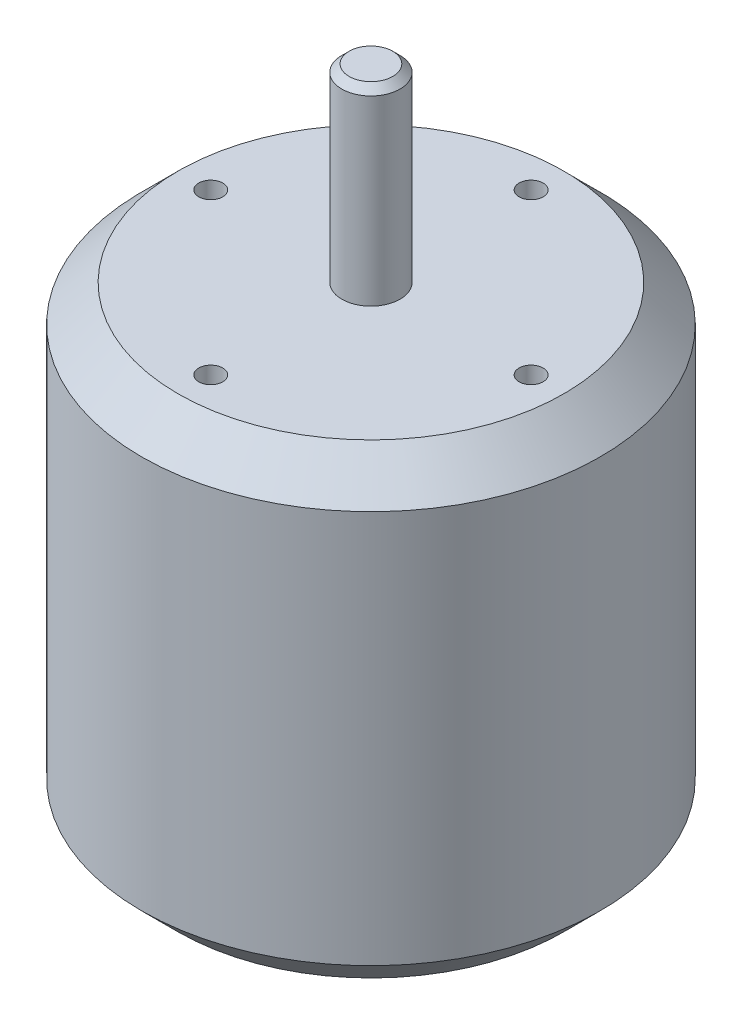
SolidWorks part; units mm, degrees
material "7050-T7451"
ref_plane "Front Plane" through (0, 0, 0) normal (0, 0, 1) x (1, 0, 0)
ref_plane "Top Plane" through (0, 0, 0) normal (0, 1, 0) x (1, 0, 0)
ref_plane "Right Plane" through (0, 0, 0) normal (1, 0, 0) x (0, 0, -1)
sketch "Sketch1" plane through (0, 0, 0) normal (0, 1, 0) x (1, 0, 0)
  circle A0 centre (0, 0) radius 31.5
  dimension "D1" = 63
extrude "Boss-Extrude1" add sketch "Sketch1" along normal blind 64
sketch "Sketch2" plane through (0, 64, 0) normal (0, 1, 0) x (1, 0, 0)
  circle A0 centre (0, 0) radius 4
  dimension "D1" = 8
extrude "Boss-Extrude2" add sketch "Sketch2" along normal blind 26
chamfer "Chamfer3" distance 1 angle 45 1 edges at (0, 90, 4)
sketch "Sketch3" plane through (0, 0, 0) normal (1, 0, 0) x (0, 0, -1)
  line L0 (3, 90) -> (-3, 90) construction
  line L1 (-1.5, 67.5) -> (1.5, 67.5)
  line L2 (-1.5, 67.5) -> (-1.5, 86.5)
  line L3 (-1.5, 86.5) -> (1.5, 86.5)
  line L4 (1.5, 67.5) -> (1.5, 86.5)
  line L5 (-1.5, 67.5) -> (1.5, 86.5) construction
  line L6 (-1.5, 86.5) -> (1.5, 67.5) construction
  line L8 (0, 90) -> (0, 64) construction
  line L9 (31.5, 64) -> (-31.5, 64) construction
  point P0 (0, 77)
  dimension "D1" = 13
  dimension "D2" = 19
  dimension "D3" = 3
extrude "Cut-Extrude1" cut sketch "Sketch3" against normal up to next
fillet "Fillet1" radius 1.5 4 edges at (-1.854, 67.5, -1.5) (-1.854, 67.5, 1.5) (-1.854, 86.5, -1.5) (-1.854, 86.5, 1.5)
sketch "Sketch7" plane through (0, 64, 0) normal (0, 1, 0) x (1, 0, 0)
  line L0 (0, 22) -> (0, 0) construction
  circle A0 centre (0, 0) radius 22 construction
  dimension "D1" = 44
hole_wizard "M4 Tapped Hole1" positions "3DSketch3" profile "Sketch10" tap size "M4" standard "DIN"
sketch3d "3DSketch3"
  point P0 (0, 64, -22)
sketch "Sketch10" plane through (0, 64, -22) normal (1, 0, 0) x (0, 0, 1)
  line L0 (0, 0) -> (0, 13.0914)
  line L1 (0, 13.0914) -> (1.65, 12.1)
  line L2 (1.65, 12.1) -> (1.65, 0)
  line L5 (1.65, 0) -> (0, 0)
  line L10 (0, 13.0914) -> (-1.65, 12.1) construction
  line L11 (0, -6.35) -> (0, 107.95) construction
  dimension "Tap Drill Dia." = 3.3
  dimension "Tap Drill Depth" = 12.1
  dimension "Drill Angle" = 118
cosmetic thread "Hole Thread1" parameters "D1"=10, "D2"=4
pattern_circular "CirPattern2" count 4 over 360 about axis through (0, 64, 0) along (0, -1, 0) of "M4 Tapped Hole1"
chamfer "Chamfer4" distance 5 angle 45 2 edges at (0, 0, 31.5) (0, 64, 31.5)
sketch "Sketch11" plane through (0, 0, 0) normal (0, -1, 0) x (-1, 0, 0)
  circle A0 centre (0, 0) radius 13
  dimension "D1" = 26
extrude "Boss-Extrude3" add sketch "Sketch11" along normal blind 7
chamfer "Chamfer5" distance 1 angle 45 1 edges at (0, -7, -13)
